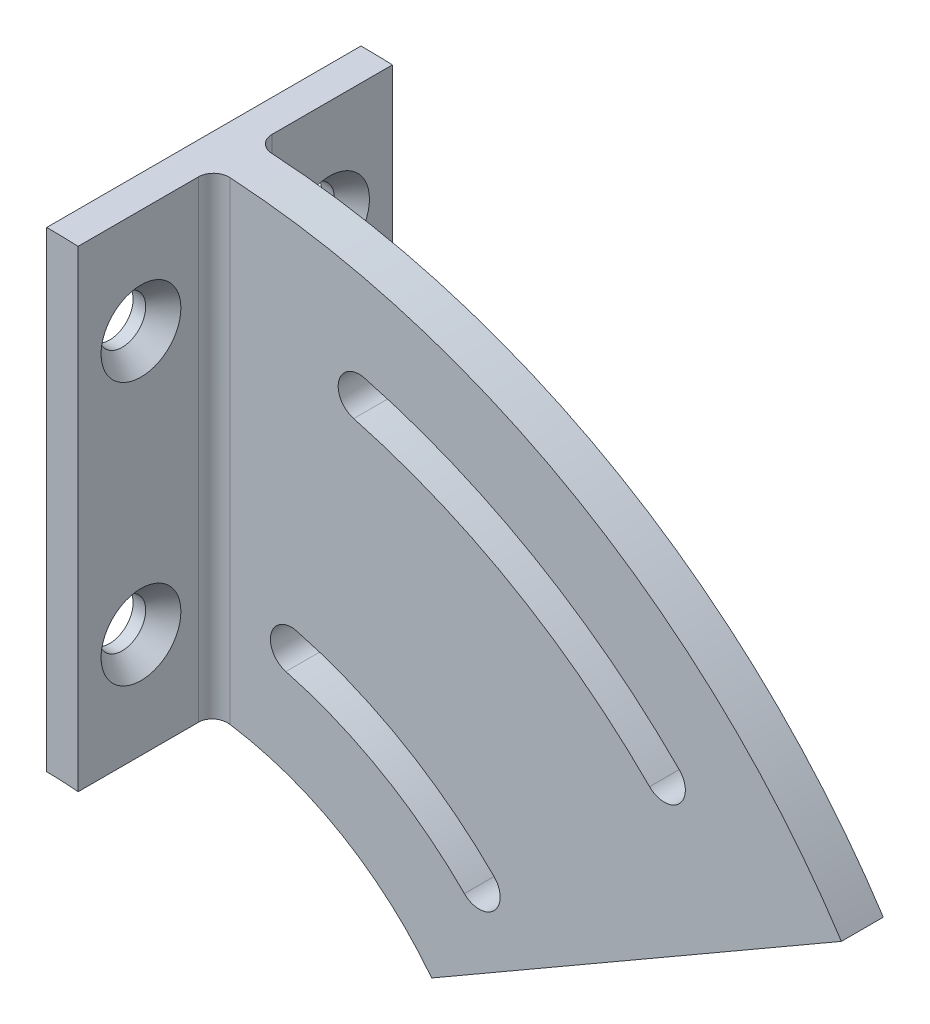
SolidWorks part; units mm, degrees
ref_plane "Front Plane" through (0, 0, 0) normal (0, 0, 1) x (1, 0, 0)
ref_plane "Top Plane" through (0, 0, 0) normal (0, 1, 0) x (1, 0, 0)
ref_plane "Right Plane" through (0, 0, 0) normal (1, 0, 0) x (0, 0, -1)
other "Configuration Table"
sketch "Sketch1" plane through (0, 0, 0) normal (0, 0, 1) x (1, 0, 0)
  line L0 (23.7488, 18.3302) -> (62.8595, 40.9107)
  line L1 (23.9808, 18.4641) -> (62.9519, 40.9641) construction
  line L2 (25.9808, 15) -> (0, 0) construction
  line L3 (0, 30) -> (0, 75)
  line L4 (0, 0) -> (45.9619, 45.9619) construction
  line L5 (25.9808, 15) -> (64.9519, 37.5)
  line L6 (3, 29.8496) -> (3, 74.94)
  line L7 (16.8232, 62.7852) -> (0, 0) construction
  line L8 (3, 30) -> (3, 75) construction
  arc A0 (23.7488, 18.3302) -> (0, 30) centre (0, 0) ccw
  arc A1 (62.8595, 40.9107) -> (0, 75) centre (0, 0) ccw
  arc A2 (25.9808, 15) -> (23.7488, 18.3302) centre (0, 0) ccw construction
  arc A3 (28.2843, 28.2843) -> (10.3528, 38.637) centre (0, 0) ccw construction
  arc A4 (29.6985, 29.6985) -> (10.8704, 40.5689) centre (0, 0) ccw
  arc A5 (26.8701, 26.8701) -> (9.8351, 36.7052) centre (0, 0) ccw
  arc A6 (26.8701, 26.8701) -> (29.6985, 29.6985) centre (28.2843, 28.2843) ccw
  arc A7 (10.8704, 40.5689) -> (9.8351, 36.7052) centre (10.3528, 38.637) ccw
  arc A8 (45.9619, 45.9619) -> (16.8232, 62.7852) centre (0, 0) ccw construction
  arc A9 (47.3762, 47.3762) -> (17.3409, 64.717) centre (0, 0) ccw
  arc A10 (44.5477, 44.5477) -> (16.3056, 60.8533) centre (0, 0) ccw
  arc A11 (44.5477, 44.5477) -> (47.3762, 47.3762) centre (45.9619, 45.9619) ccw
  arc A12 (17.3409, 64.717) -> (16.3056, 60.8533) centre (16.8232, 62.7852) ccw
  point P14 (20, 34.641)
  point P19 (32.5, 56.2917)
  point P26 (0, 0)
  dimension "D2" = 75
  dimension "D7" = 10
  dimension "D8" = 25
  dimension "D9" = 2
  dimension "D1" = 30
  dimension "D4" = 60
  dimension "D5" = 45
  dimension "D6" = 30
  dimension "D3" = 4
  dimension "D10" = 3
extrude "Boss-Extrude1" add sketch "Sketch1" along normal mid plane 4 contours L0 A1 L6 A0 A12 A9 A11 A10 A7 A4 A6 A5 region at (26.6184, 47.196, 0)
extrude "Boss-Extrude2" add sketch "Sketch1<3>" along normal mid plane 30 contours L6 A1 L3 A0 region at (1.5005, 52.4649, 0)
sketch "Sketch1<3>" plane through (0, 0, 0) normal (0, 0, 1) x (1, 0, 0) same geometry as "Sketch1"
sketch "Sketch2" plane through (3, 0, 0) normal (1, 0, 0) x (0, 0, -1)
  line L0 (-15, 29.8496) -> (-15, 74.94) construction
  line L1 (15, 29.8496) -> (15, 74.94) construction
  line L2 (2, 74.94) -> (15, 74.94) construction
  line L3 (2, 29.8496) -> (15, 29.8496) construction
  point P0 (-9, 64.94)
  point P2 (9, 64.94)
  point P4 (9, 39.8496)
  point P6 (-9, 39.8496)
  point P9 (0, 0)
  point P10 (0, 0)
  point P11 (0, 0)
  point P12 (0, 0)
  point P13 (0, 0)
  dimension "D1" = 6
  dimension "D2" = 6
  dimension "D3" = 10
  dimension "D4" = 10
hole_wizard "CSK for #8 Flat Head Socket Cap Screw1" positions "Sketch2" profile "Sketch3" countersink size "#8" standard "ANSI Inch"
sketch "Sketch3" plane through (3, 64.94, 9) normal (0, 1, 0) x (0, 0, -1)
  line L0 (0, 0) -> (0, 15.7088)
  line L1 (0, 15.7088) -> (2.2479, 15)
  line L2 (2.2479, 15) -> (2.2479, 1.797)
  line L3 (2.2479, 1.797) -> (3.81, 0)
  line L5 (3.81, 0) -> (0, 0)
  line L6 (-2.2479, 1.797) -> (-3.81, 0) construction
  line L10 (0, 15.7088) -> (-2.2479, 15) construction
  line L11 (0, -6.35) -> (0, 107.95) construction
  dimension "Hole Dia." = 4.4958
  dimension "Hole Depth" = 15
  dimension "Near C'Sink Dia." = 7.62
  dimension "Near C'Sink Angle" = 82
  dimension "Drill Angle" = 145
fillet "Fillet1" radius 1.5 2 edges at (3, 52.3948, 2) (3, 52.3948, -2)
